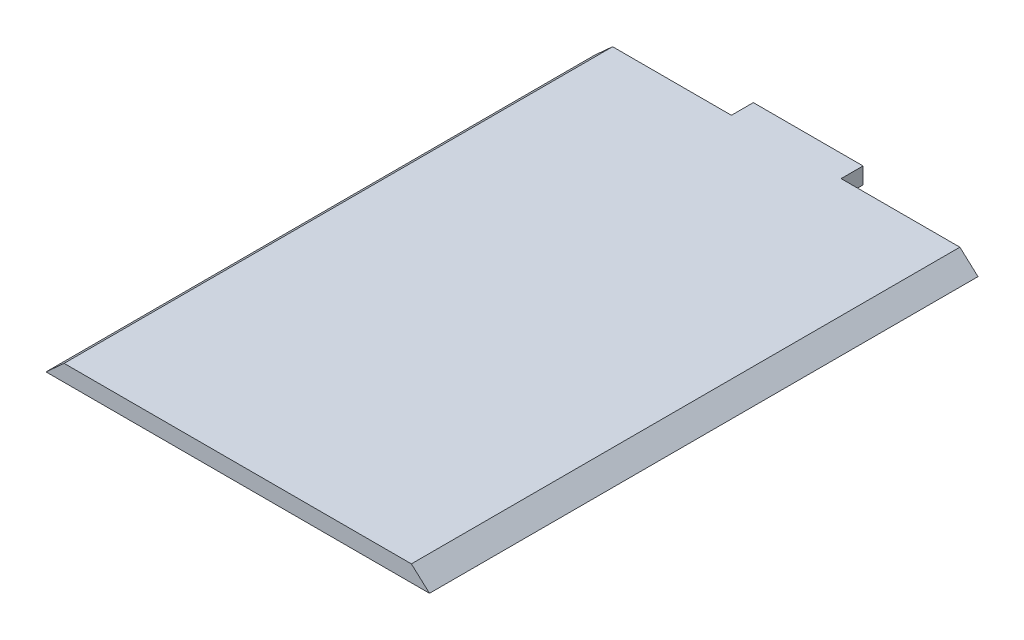
SolidWorks part; units mm, degrees
ref_plane "Front Plane" through (0, 0, 0) normal (0, 0, 1) x (1, 0, 0)
ref_plane "Top Plane" through (0, 0, 0) normal (0, 1, 0) x (1, 0, 0)
ref_plane "Right Plane" through (0, 0, 0) normal (1, 0, 0) x (0, 0, -1)
sketch "Sketch1" plane through (0, 0, 0) normal (0, 0, 1) x (1, 0, 0)
  line L0 (0, 0) -> (0, 44.45) construction
  line L1 (-40.2039, 5.9378) -> (40.2039, 5.9378)
  line L2 (-44.399, 2.1278) -> (44.399, 2.1278)
  line L3 (-40.2039, 5.9378) -> (-44.399, 2.1278)
  line L4 (40.2039, 5.9378) -> (44.399, 2.1278)
  arc A0 (44.399, 2.1278) -> (-44.399, 2.1278) centre (0, 0) ccw construction
  arc A1 (40.2039, 5.9378) -> (-40.2039, 5.9378) centre (0, 0) ccw construction
  dimension "D1" = 88.9
  dimension "D2" = 3.81
  dimension "D3" = 3.81
extrude "Boss-Extrude1" add sketch "Sketch1" along normal blind 127
sketch "Sketch2" plane through (0, 2.1278, 0) normal (0, -1, 0) x (1, 0, 0)
  line L0 (-44.399, 0) -> (44.399, 0) construction
  line L1 (-12.7, 0) -> (12.7, 0)
  line L2 (-12.7, 0) -> (-12.7, -5.08)
  line L3 (-12.7, -5.08) -> (12.7, -5.08)
  line L4 (12.7, 0) -> (12.7, -5.08)
  line L5 (0, 0) -> (0, -5.08) construction
  line L6 (0, 0) -> (0, 127) construction
  line L7 (-44.399, 127) -> (44.399, 127) construction
  dimension "D1" = 25.4
  dimension "D2" = 5.08
  dimension "D3" = 0
extrude "Boss-Extrude2" add sketch "Sketch2" against normal blind 3.81
